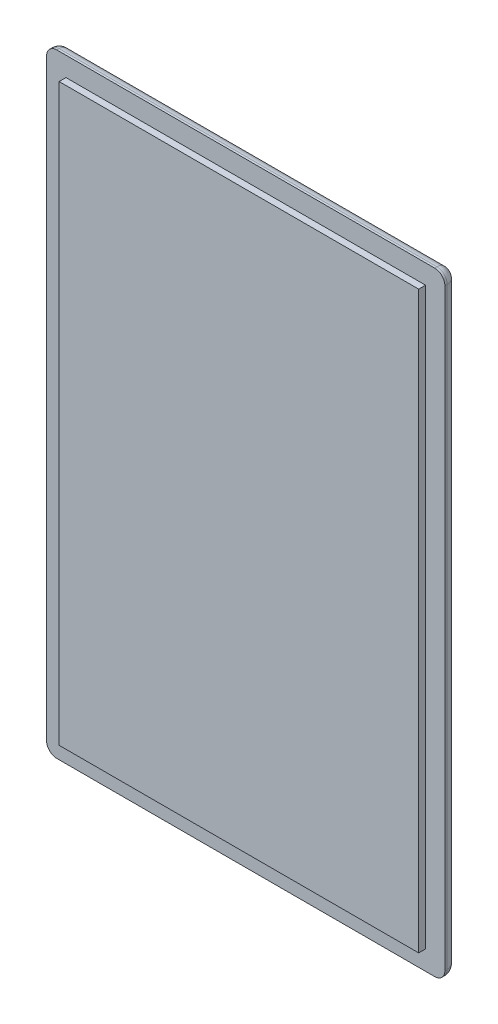
SolidWorks part; units mm, degrees
ref_plane "Front Plane" through (0, 0, 0) normal (0, 0, 1) x (1, 0, 0)
ref_plane "Top Plane" through (0, 0, 0) normal (0, 1, 0) x (1, 0, 0)
ref_plane "Right Plane" through (0, 0, 0) normal (1, 0, 0) x (0, 0, -1)
sketch "Sketch1" plane through (0, 0, 0) normal (0, 0, 1) x (1, 0, 0)
  line L1 (0, 0) -> (370, 0)
  line L2 (0, 0) -> (0, 570)
  line L3 (0, 570) -> (370, 570)
  line L4 (370, 0) -> (370, 570)
  dimension "D1" = 370
  dimension "D2" = 570
extrude "Boss-Extrude1" add sketch "Sketch1" along normal blind 18
sketch "Sketch2" plane through (0, 0, 18) normal (0, 0, 1) x (1, 0, 0)
  line L1 (18, 552) -> (352, 552)
  line L2 (18, 552) -> (18, 18)
  line L3 (18, 18) -> (352, 18)
  line L4 (352, 552) -> (352, 18)
  line L5 (0, 570) -> (370, 570)
  line L6 (0, 570) -> (0, 0)
  line L7 (0, 0) -> (370, 0)
  line L8 (370, 570) -> (370, 0)
  dimension "D1" = 18
  dimension "D2" = 18
  dimension "D3" = 18
  dimension "D4" = 18
extrude "Cut-Extrude1" cut sketch "Sketch2" against normal blind 6.35
fillet "Fillet1" radius 9.525 8 edges at (0, 570, 5.825) (185, 570, 0) (370, 570, 5.825) (370, 285, 0) (0, 285, 0) (185, 0, 0) (0, 0, 5.825) (370, 0, 5.825)
